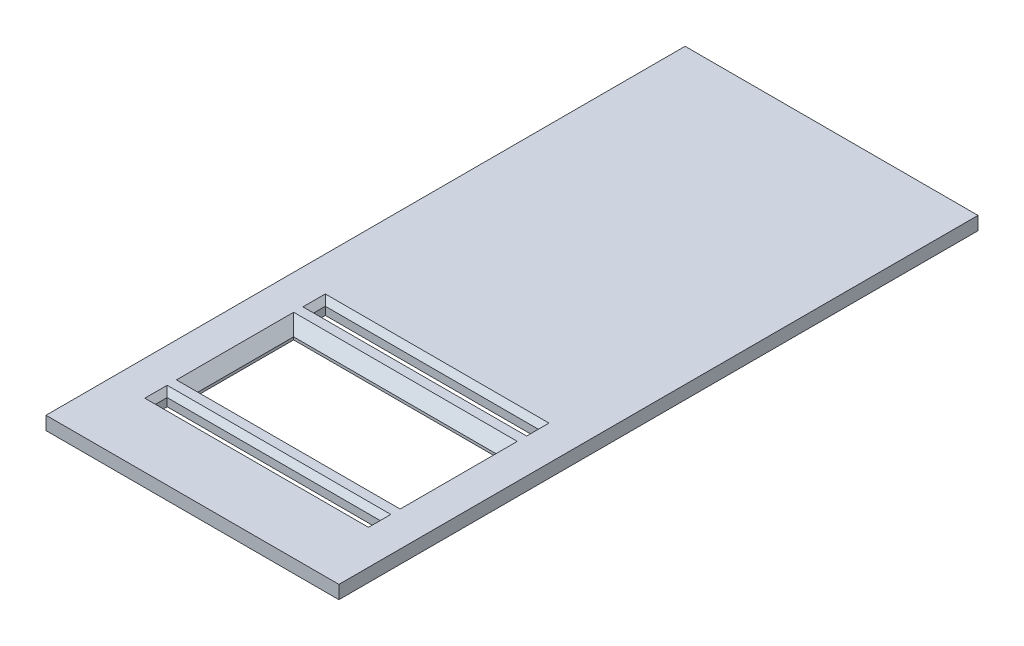
SolidWorks part; units mm, degrees
ref_plane "Front Plane" through (0, 0, 0) normal (0, 0, 1) x (1, 0, 0)
ref_plane "Top Plane" through (0, 0, 0) normal (0, 1, 0) x (1, 0, 0)
ref_plane "Right Plane" through (0, 0, 0) normal (1, 0, 0) x (0, 0, -1)
sketch "Sketch1" plane through (0, 0, 0) normal (0, 1, 0) x (1, 0, 0)
  line L1 (-69.85, -50.8) -> (69.85, -50.8)
  line L2 (-69.85, -50.8) -> (-69.85, 254)
  line L3 (-69.85, 254) -> (69.85, 254)
  line L4 (69.85, -50.8) -> (69.85, 254)
  line L5 (0, 254) -> (0, -50.8) construction
  line L6 (-69.85, 101.6) -> (69.85, 101.6) construction
  point P0 (0, 101.6)
  dimension "D1" = 304.8
  dimension "D2" = 139.7
  dimension "D3" = 101.6
extrude "Boss-Extrude1" add sketch "Sketch1" along normal blind 6.35
sketch "Sketch2" plane through (0, 6.35, 0) normal (0, 1, 0) x (1, 0, 0)
  line L0 (-69.85, -50.8) -> (69.85, -50.8) construction
  line L1 (-48.26, 0) -> (48.26, 0)
  line L2 (-48.26, 0) -> (-48.26, 45.72)
  line L3 (-48.26, 45.72) -> (48.26, 45.72)
  line L4 (48.26, 0) -> (48.26, 45.72)
  line L5 (0, 45.72) -> (0, 0) construction
  line L6 (-48.26, 22.86) -> (48.26, 22.86) construction
  point P0 (0, 22.86)
  dimension "D1" = 45.72
  dimension "D2" = 96.52
  dimension "D3" = 50.8
extrude "Main Hole" cut sketch "Sketch2" against normal through all
ref_plane "Plane1" through (0, 0, -22.86) normal (0, 0, 1) x (1, 0, 0)
sketch "Sketch3" plane through (0, 6.35, 0) normal (0, 1, 0) x (1, 0, 0)
  line L0 (48.26, 45.72) -> (-48.26, 45.72) construction
  line L1 (-50.8, 57.785) -> (50.8, 57.785)
  line L2 (-50.8, 57.785) -> (-50.8, 63.373)
  line L3 (-50.8, 63.373) -> (50.8, 63.373)
  line L4 (50.8, 57.785) -> (50.8, 63.373)
  point P4 (0, 57.785)
  dimension "D1" = 101.6
  dimension "D2" = 5.588
  dimension "D3" = 12.065
extrude "NeoPixel" cut sketch "Sketch3" against normal through all
mirror "Mirror2" about plane through (0, 0, -22.86) normal (0, 0, 1) of "NeoPixel"
sketch "Sketch5" plane through (0, 0, 0) normal (0, -1, 0) x (1, 0, 0)
  line L0 (69.85, -254) -> (-69.85, -254) construction
  line L1 (67.31, -251.46) -> (-67.31, -251.46)
  line L2 (67.31, -251.46) -> (67.31, 48.26)
  line L3 (67.31, 48.26) -> (-67.31, 48.26)
  line L4 (-67.31, -251.46) -> (-67.31, 48.26)
  line L5 (64.77, -248.92) -> (-64.77, -248.92)
  line L6 (64.77, -248.92) -> (64.77, 45.72)
  line L7 (64.77, 45.72) -> (-64.77, 45.72)
  line L8 (-64.77, -248.92) -> (-64.77, 45.72)
  line L9 (-69.85, -254) -> (-69.85, 50.8) construction
  line L10 (-69.85, 50.8) -> (69.85, 50.8) construction
  line L11 (69.85, 50.8) -> (69.85, -254) construction
  dimension "D1" = 2.54
  dimension "D2" = 2.54
  dimension "D3" = 2.54
  dimension "D4" = 2.54
  dimension "D5" = 2.54
  dimension "D6" = 2.54
  dimension "D7" = 2.54
  dimension "D8" = 2.54
extrude "Boss-Extrude2" [suppressed] add sketch "Sketch5" along normal blind 2.54 contours L4 L1 L2 L3 L5 L8 L7 L6
chamfer "Chamfer1" distance 2.54 angle 45 8 edges at (50.8, 6.35, 14.859) (0, 6.35, 17.653) (-50.8, 6.35, 14.859) (0, 6.35, 12.065) (-50.8, 6.35, -60.579) (0, 6.35, -57.785) (50.8, 6.35, -60.579) (0, 6.35, -63.373)
chamfer "Chamfer2" distance 5.08 angle 45 4 edges at (48.26, 6.35, -22.86) (0, 6.35, 0) (-48.26, 6.35, -22.86) (0, 6.35, -45.72)
sketch "Sketch6" plane through (0, 0, 0) normal (0, -1, 0) x (1, 0, 0)
  line L0 (0.6985, -22.86) -> (-0.6985, -22.86) construction
  line L1 (50.8, 2.54) -> (-50.8, 2.54)
  line L2 (50.8, 2.54) -> (50.8, -48.26)
  line L3 (50.8, -48.26) -> (-50.8, -48.26)
  line L4 (-50.8, 2.54) -> (-50.8, -48.26)
  line L5 (0, -48.26) -> (0, 2.54) construction
  line L6 (50.8, -22.86) -> (-50.8, -22.86) construction
  line L7 (0, -4.8895) -> (0, 4.8895) construction
  line L8 (6.35, -50.8) -> (6.35, -48.26)
  line L9 (53.34, 5.08) -> (-53.34, 5.08)
  line L10 (53.34, 5.08) -> (53.34, -50.8)
  line L11 (53.34, -50.8) -> (-53.34, -50.8)
  line L12 (-53.34, 5.08) -> (-53.34, -50.8)
  line L13 (0, -50.8) -> (0, 5.08) construction
  line L14 (53.34, -22.86) -> (-53.34, -22.86) construction
  line L31 (-6.35, -50.8) -> (-6.35, -48.26)
  line L32 (6.35, -49.53) -> (-6.35, -49.53) construction
  point P0 (0, -22.86)
  point P8 (0, -22.86)
  point P16 (0, -49.53)
  dimension "D1" = 2.54
  dimension "D2" = 2.54
  dimension "D3" = 50.8
  dimension "D4" = 101.6
  dimension "D5" = 12.7
extrude "Boss-Extrude3" [suppressed] add sketch "Sketch6" along normal blind 4.064 contours L9 L12 L11 L10 L4 L1 L2 L3
equation "\"D1@Sketch2\"=1.8in"
equation "\"D2@Sketch2\"=3.8in"
